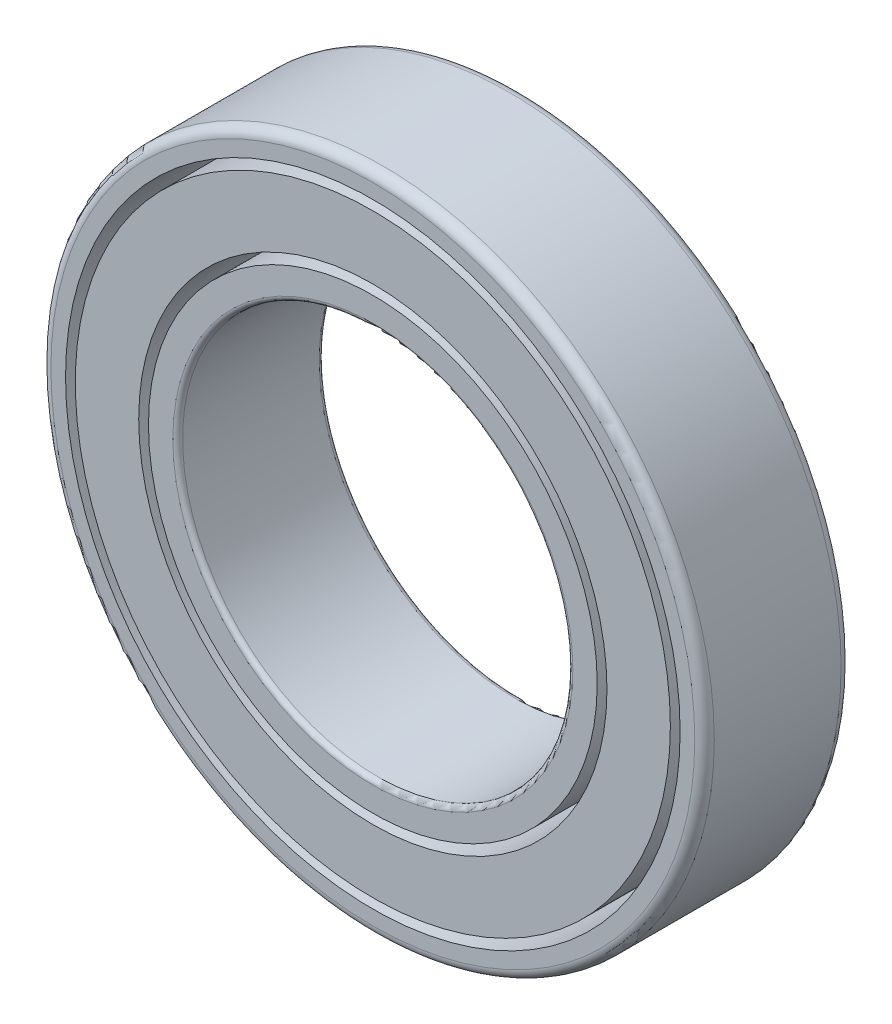
SolidWorks part; units mm, degrees
material "AISI 304"
ref_plane "Alzado" through (0, 0, 0) normal (0, 0, 1) x (1, 0, 0)
ref_plane "Planta" through (0, 0, 0) normal (0, 1, 0) x (1, 0, 0)
ref_plane "Vista lateral" through (0, 0, 0) normal (1, 0, 0) x (0, 0, -1)
sketch "Croquis1" plane through (0, 0, 0) normal (0, 0, 1) x (1, 0, 0)
  circle A0 centre (0, 0) radius 20
  circle A1 centre (0, 0) radius 31.5
  circle A2 centre (0, 0) radius 23
  circle A3 centre (0, 0) radius 24
  circle A4 centre (0, 0) radius 30.5
  circle A5 centre (0, 0) radius 34
  dimension "D1" = 40
  dimension "D2" = 61
  dimension "D3" = 46
  dimension "D4" = 48
  dimension "D5" = 63
  dimension "D6" = 68
extrude "Saliente-Extruir1" add sketch "Croquis1" along normal mid plane 15 contours A4 A3 | A2 A0 | A5 | A1 region at (-22.3495, 0, 0) region at (-29.6373, 0, 0)
fillet "Redondeo1" radius 1 2 edges at (34, 0, -7.5) (34, 0, 7.5)
fillet "Redondeo2" radius 0.5 2 edges at (20, 0, -7.5) (20, 0, 7.5)
